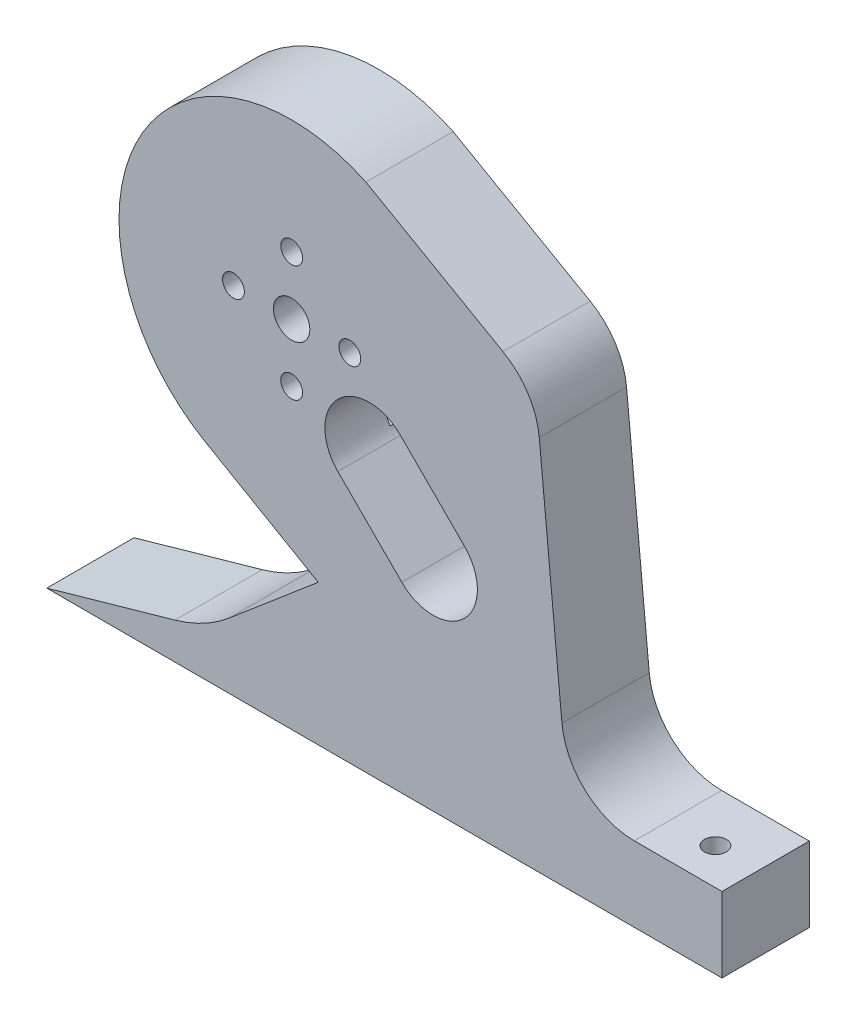
SolidWorks part; units mm, degrees
ref_plane "Front Plane" through (0, 0, 0) normal (0, 0, 1) x (1, 0, 0)
ref_plane "Top Plane" through (0, 0, 0) normal (0, 1, 0) x (1, 0, 0)
ref_plane "Right Plane" through (0, 0, 0) normal (1, 0, 0) x (0, 0, -1)
sketch "Sketch1" plane through (0, 0, 0) normal (0, 0, 1) x (1, 0, 0)
  line L0 (-3.1165, 51.7901) -> (-1.6309, 36.3244)
  line L4 (-8.1116, 59.5177) -> (-33.5078, 19.3458)
  line L5 (-26.9509, 70.2764) -> (-8.1116, 59.5177)
  line L6 (-1.6309, 36.3244) -> (0, 19.3458)
  line L7 (9.9542, 10.3019) -> (22, 10.3019)
  line L9 (-49.0189, 28.3011) -> (-33.5078, 19.3458)
  line L10 (-33.5078, 19.3458) -> (0, 0)
  line L11 (22, 10.3019) -> (22, 0)
  line L12 (22, 0) -> (0, 0)
  line L13 (0, 0) -> (-70.8223, 0)
  line L14 (-33.5078, 19.3458) -> (-45.7172, 8.9956)
  line L15 (-53.1824, 5.0134) -> (-70.8223, 0)
  arc A1 (-49.0189, 28.3011) -> (-26.9509, 70.2764) centre (-37.1539, 48.8518) cw
  arc A2 (0, 19.3458) -> (9.9542, 10.3019) centre (9.9542, 20.3019) ccw
  arc A3 (-3.1165, 51.7901) -> (-8.1116, 59.5177) centre (-13.0707, 50.8339) ccw
  arc A6 (-45.7172, 8.9956) -> (-53.1824, 5.0134) centre (-58.65, 24.2515) cw
  dimension "D3" = 23.73
  dimension "D6" = 10
  dimension "D7" = 10
  dimension "D8" = 12.0458
  dimension "D12" = 20
  dimension "D1" = 49.0189
  dimension "D2" = 22
  dimension "D4" = 10.3019
  dimension "D5" = 21.6949
  dimension "D11" = 70.8223
extrude "Boss-Extrude2" add sketch "Sketch1" against normal blind 12 contours L10 L12 L11 L7 A2 L6 L0 A3 L4
extrude "Boss-Extrude3" add sketch "Sketch1<8>" against normal blind 12 separate body contours L4 L9 A1 L5
sketch "Sketch1<8>" plane through (0, 0, 0) normal (0, 0, 1) x (1, 0, 0) same geometry as "Sketch1"
extrude "Boss-Extrude5" add sketch "Sketch1<10>" against normal up to surface (12 mm away) contours L15 L13 L10 L14 A6 up to face at (1.0515, 21.1611, -12)
sketch "Sketch1<10>" plane through (0, 0, 0) normal (0, 0, 1) x (1, 0, 0) same geometry as "Sketch1"
sketch "Sketch14" plane through (0, 0, -12) normal (0, 0, -1) x (-1, 0, 0)
  circle A0 centre (37.1539, 48.8518) radius 15
  dimension "D1" = 30
extrude "Cut-Extrude5" cut sketch "Sketch14" against normal blind 4
sketch "Sketch16" plane through (0, 0, -8) normal (0, 0, -1) x (-1, 0, 0)
  circle A0 centre (37.1539, 48.8518) radius 2.5
extrude "Cut-Extrude7" cut sketch "Sketch16" against normal up to surface (8 mm away) up to face at (-21.4366, 24.3401, 0)
sketch "Sketch15" plane through (0, 0, -8) normal (0, 0, -1) x (-1, 0, 0)
  circle A0 centre (37.1539, 56.8518) radius 1.5
  circle A1 centre (45.1539, 48.8518) radius 1.5
  circle A2 centre (37.1539, 40.8518) radius 1.5
  circle A3 centre (29.1539, 48.8518) radius 1.5
  point P3 (37.1539, 48.8518)
  point P13 (37.1539, 48.8518)
  dimension "D1" = 3
  dimension "D2" = 8
  dimension "D3" = 4
extrude "Cut-Extrude6" cut sketch "Sketch15" against normal up to surface (8 mm away) up to face at (-34.6539, 48.8518, 0)
sketch "Sketch19" plane through (0, 10.3019, 0) normal (0, 1, 0) x (1, 0, 0)
  line L1 (22, 0) -> (0, 0) construction
  circle A0 centre (16.0971, 5) radius 1.5
  dimension "D1" = 3
  dimension "D2" = 5
extrude "Cut-Extrude9" cut sketch "Sketch19" against normal up to surface (10.3019 mm away) up to face at (-24.4112, 0, -6)
sketch "Sketch20" plane through (0, 0, 0) normal (0, 0, 1) x (1, 0, 0)
  line L0 (-37.1539, 48.8518) -> (-17.7084, 29.4064) construction
  line L1 (-17.7084, 29.4064) -> (-26.5023, 38.2003) construction
  line L2 (-22.0106, 25.1042) -> (-30.8045, 33.8981)
  line L3 (-13.4062, 33.7086) -> (-22.2001, 42.5025)
  arc A0 (-22.0106, 25.1042) -> (-13.4062, 33.7086) centre (-17.7084, 29.4064) ccw
  arc A1 (-22.2001, 42.5025) -> (-30.8045, 33.8981) centre (-26.5023, 38.2003) ccw
  point P2 (-22.1054, 33.8033)
  dimension "D2" = 12.4364
  dimension "D3" = 6.0842
  dimension "D1" = 27.5
extrude "Cut-Extrude10" cut sketch "Sketch20" against normal up to surface (12 mm away) up to face at (-52.1539, 48.8518, -12)
